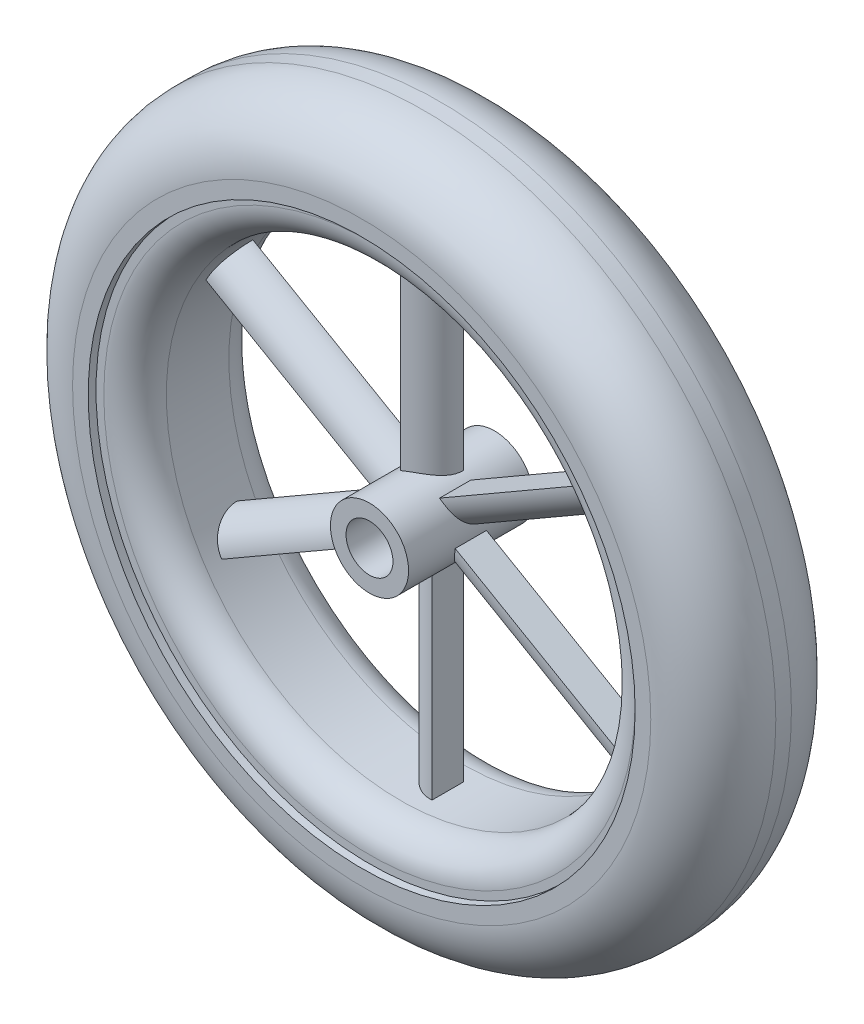
SolidWorks part; units mm, degrees
ref_plane "Front Plane" through (0, 0, 0) normal (0, 0, 1) x (1, 0, 0)
ref_plane "Top Plane" through (0, 0, 0) normal (0, 1, 0) x (1, 0, 0)
ref_plane "Right Plane" through (0, 0, 0) normal (1, 0, 0) x (0, 0, -1)
sketch "Sketch1" plane through (0, 0, 0) normal (0, 0, 1) x (1, 0, 0)
  circle A0 centre (0, 0) radius 1.5
  circle A1 centre (0, 0) radius 2.5
  dimension "D1" = 3
  dimension "D2" = 5
extrude "Boss-Extrude1" add sketch "Sketch1" along normal mid plane 8
sketch "Sketch2" plane through (0, 0, 0) normal (0, 0, 1) x (1, 0, 0)
  circle A0 centre (0, 0) radius 17.5
  circle A1 centre (0, 0) radius 15
  dimension "D1" = 30
  dimension "D2" = 35
extrude "Boss-Extrude2" add sketch "Sketch2" along normal mid plane 8 separate body
sketch "Sketch3" plane through (0, 0, 0) normal (0, 0, 1) x (1, 0, 0)
  line L1 (-1, 2.2913) -> (-1, 14.9666)
  line L3 (1, 14.9666) -> (1, 2.2913)
  line L4 (1.4843, 2.0117) -> (12.4615, 8.3493)
  line L5 (13.4615, 6.6173) -> (2.4843, 0.2796)
  line L6 (2.4843, -0.2796) -> (13.4615, -6.6173)
  line L7 (12.4615, -8.3493) -> (1.4843, -2.0117)
  line L8 (1, -2.2913) -> (1, -14.9666)
  line L9 (-1, -14.9666) -> (-1, -2.2913)
  line L10 (-1.4843, -2.0117) -> (-12.4615, -8.3493)
  line L11 (-13.4615, -6.6173) -> (-2.4843, -0.2796)
  line L12 (-2.4843, 0.2796) -> (-13.4615, 6.6173)
  line L13 (-12.4615, 8.3493) -> (-1.4843, 2.0117)
  arc A0 (1, 14.9666) -> (-1, 14.9666) centre (0, 0) ccw
  arc A1 (13.4615, 6.6173) -> (12.4615, 8.3493) centre (0, 0) ccw
  arc A2 (-1.4843, 2.0117) -> (-2.4843, 0.2796) centre (0, 0) ccw
  arc A3 (12.4615, -8.3493) -> (13.4615, -6.6173) centre (0, 0) ccw
  arc A4 (-1, -14.9666) -> (1, -14.9666) centre (0, 0) ccw
  arc A5 (-13.4615, -6.6173) -> (-12.4615, -8.3493) centre (0, 0) ccw
  arc A6 (-12.4615, 8.3493) -> (-13.4615, 6.6173) centre (0, 0) ccw
  arc A7 (1, 2.2913) -> (-1, 2.2913) centre (0, 0) ccw
  arc A8 (2.4843, 0.2796) -> (1.4843, 2.0117) centre (0, 0) ccw
  arc A9 (1.4843, -2.0117) -> (2.4843, -0.2796) centre (0, 0) ccw
  arc A10 (-1, -2.2913) -> (1, -2.2913) centre (0, 0) ccw
  arc A11 (-2.4843, -0.2796) -> (-1.4843, -2.0117) centre (0, 0) ccw
  point P29 (0, 0)
  dimension "D1" = 6
extrude "Boss-Extrude5" add sketch "Sketch3" along normal mid plane 2
fillet "Fillet1" radius 2 2 edges at (15, 0, -4) (15, 0, 4)
fillet "Fillet2" radius 2 6 edges at (-1, -8.629, 1) (6.9729, -5.1805, 1) (7.9729, 3.4485, 1) (1, 8.629, 1) (-6.9729, 5.1805, 1) (-7.9729, -3.4485, 1)
sketch "Sketch4" plane through (0, 0, 0) normal (0, 0, 1) x (1, 0, 0)
  circle A0 centre (0, 0) radius 17.5
  circle A1 centre (0, 0) radius 22.5
  dimension "D1" = 45
  dimension "D2" = 35
extrude "Boss-Extrude6" add sketch "Sketch4" along normal mid plane 9
fillet "Fillet3" radius 4 2 edges at (22.5, 0, -4.5) (22.5, 0, 4.5)
